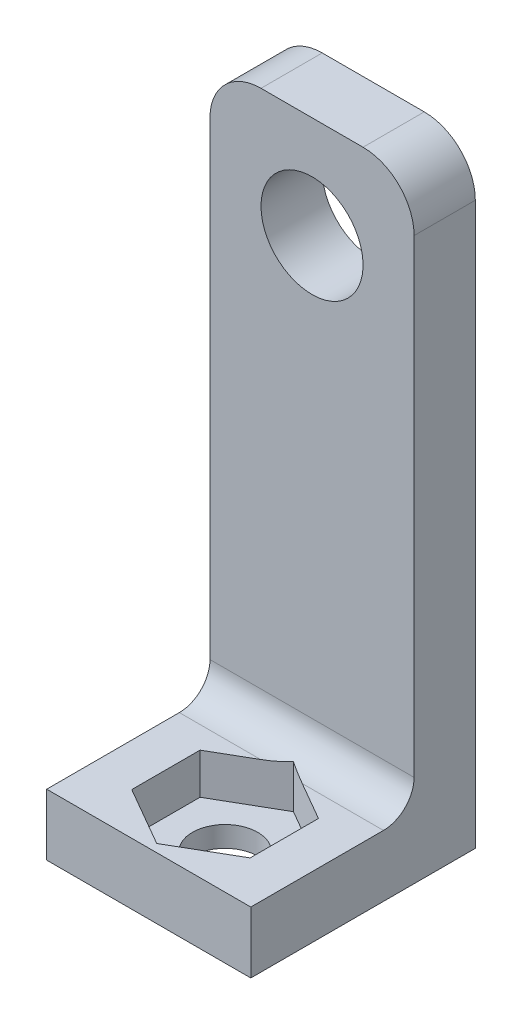
SolidWorks part; units mm, degrees
ref_plane "Спереди" through (0, 0, 0) normal (0, 0, 1) x (1, 0, 0)
ref_plane "Сверху" through (0, 0, 0) normal (0, 1, 0) x (1, 0, 0)
ref_plane "Справа" through (0, 0, 0) normal (1, 0, 0) x (0, 0, -1)
sketch "Эскиз1" plane through (0, 0, 0) normal (0, 0, 1) x (1, 0, 0)
  line L1 (-5, 15) -> (5, 15)
  line L2 (-5, 15) -> (-5, -15)
  line L3 (-5, -15) -> (5, -15)
  line L4 (5, 15) -> (5, -15)
  line L5 (-5, 15) -> (5, -15) construction
  line L6 (-5, -15) -> (5, 15) construction
  point P0 (0, 0)
  dimension "D1" = 10
  dimension "D2" = 30
extrude "Бобышка-Вытянуть1" add sketch "Эскиз1" along normal blind 3
sketch "Эскиз2" plane through (0, 0, 0) normal (0, 0, -1) x (-1, 0, 0)
  circle A0 centre (0, 10) radius 2.5
  dimension "D1" = 25
extrude "Вырез-Вытянуть1" cut sketch "Эскиз2" against normal blind 3
fillet "Скругление2" radius 2.5 1 edges at (5, 15, 1.5)
fillet "Скругление3" radius 2.5 1 edges at (-5, 15, 1.5)
sketch "Эскиз3" plane through (0, 0, 3) normal (0, 0, 1) x (1, 0, 0)
  line L0 (5, -15) -> (5, 12.5) construction
  line L1 (-5, -15) -> (5, -15)
  line L2 (-5, -15) -> (-5, -11.9885)
  line L3 (-5, -11.9885) -> (5, -11.9885)
  line L4 (5, -15) -> (5, -11.9885)
extrude "Бобышка-Вытянуть2" add sketch "Эскиз3" along normal blind 8
sketch "Эскиз4" plane through (0, -11.9885, 0) normal (0, 1, 0) x (1, 0, 0)
  line L0 (-5, -11) -> (5, 0) construction
  line L1 (5, 0) -> (-6.05, 0) construction
  line L2 (-2.5, 0) -> (-5, 0) construction
  line L3 (-6.05, 0) -> (6.05, -11) construction
  line L4 (5, -11) -> (-5, -11) construction
  line L5 (0, -5.5) -> (0, -11.2719) construction
  circle A0 centre (0, -7.2592) radius 1.6
extrude "Вырез-Вытянуть2" cut sketch "Эскиз4" against normal blind 7
sketch "Эскиз6" plane through (0, -11.9885, 0) normal (0, 1, 0) x (1, 0, 0)
  line L1 (2.9, -8.9335) -> (2.9, -5.5849)
  line L2 (2.9, -5.5849) -> (0, -3.9106)
  line L3 (0, -3.9106) -> (-2.9, -5.5849)
  line L4 (-2.9, -5.5849) -> (-2.9, -8.9335)
  line L5 (-2.9, -8.9335) -> (0, -10.6078)
  line L6 (0, -10.6078) -> (2.9, -8.9335)
  circle A0 centre (0, -7.2592) radius 2.9 construction
  dimension "D1" = 5.8
extrude "Вырез-Вытянуть3" cut sketch "Эскиз6" against normal blind 2
fillet "Скругление4" radius 1.5 1 edges at (0, -11.9885, 3)
